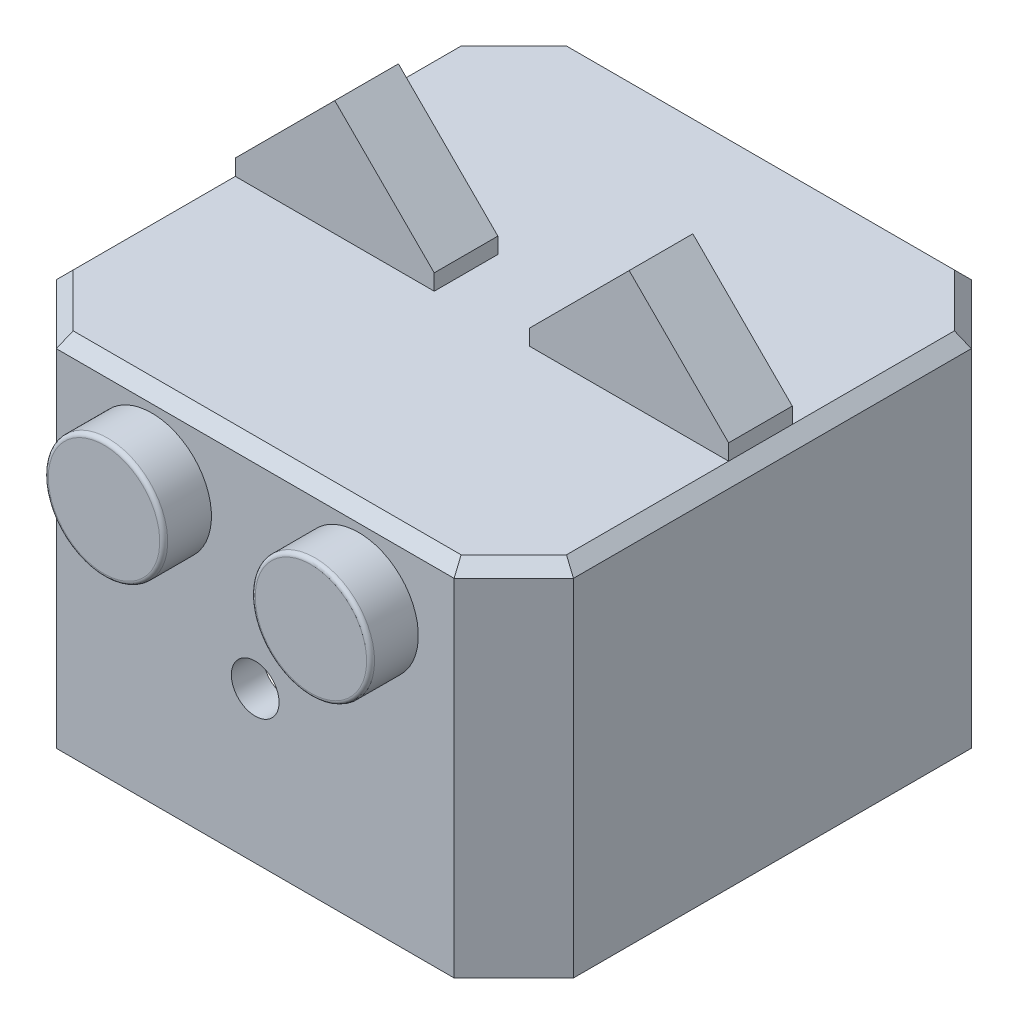
SolidWorks part; units mm, degrees
ref_plane "Alzado" through (0, 0, 0) normal (0, 0, 1) x (1, 0, 0)
ref_plane "Planta" through (0, 0, 0) normal (0, 1, 0) x (1, 0, 0)
ref_plane "Vista lateral" through (0, 0, 0) normal (1, 0, 0) x (0, 0, -1)
sketch "Croquis1" plane through (0, 0, 0) normal (0, 1, 0) x (1, 0, 0)
  line L1 (-25, -32.5) -> (25, -32.5)
  line L3 (-25, 32.5) -> (25, 32.5)
  line L5 (-25, -32.5) -> (25, 32.5) construction
  line L6 (-25, 32.5) -> (25, -32.5) construction
  line L10 (32.5, 25) -> (32.5, -25)
  line L11 (25, -32.5) -> (32.5, -25)
  line L12 (32.5, 25) -> (25, 32.5)
  line L13 (-32.5, 25) -> (-32.5, -25)
  line L14 (-32.5, -25) -> (-25, -32.5)
  line L15 (-32.5, 25) -> (-25, 32.5)
  point P0 (0, 0)
  point P10 (0, 32.5)
  dimension "D1" = 65
  dimension "D2" = 65
  dimension "D3" = 50
  dimension "D4" = 50
  dimension "D5" = 25
  dimension "D6" = 25
extrude "Saliente-Extruir1" add sketch "Croquis1" along normal blind 45
shell "Vaciado2" thickness 4 removed face at (0, 0, 0)
chamfer "Chaflán3" distance 1.5 angle 45 8 edges at (0, 45, -32.5) (32.5, 45, 0) (0, 45, 32.5) (-32.5, 45, 0) (-28.75, 45, 28.75) (28.75, 45, 28.75) (28.75, 45, -28.75) (-28.75, 45, -28.75)
sketch "Croquis2" plane through (0, 0, 32.5) normal (0, 0, 1) x (1, 0, 0)
  line L0 (0, 0) -> (0, 6.916) construction
  circle A0 centre (13, 35) radius 7.5
  circle A1 centre (-13, 35) radius 7.5
  dimension "D1" = 15
  dimension "D2" = 13
  dimension "D3" = 35
extrude "Saliente-Extruir2" add sketch "Croquis2" along normal blind 6
sketch "Croquis4" plane through (0, 0, 28.5) normal (0, 0, -1) x (-1, 0, 0)
  line L0 (0, 0) -> (0, 4.7403) construction
  line L1 (0, 0) -> (0, 6.916) construction
  circle A0 centre (-13, 35) radius 5
  circle A1 centre (13, 35) radius 5
  dimension "D1" = 10
extrude "Cortar-Extruir2" cut sketch "Croquis4" against normal blind 5.5
fillet "Redondeo1" radius 0.5 2 edges at (-20.5, 35, 38.5) (20.5, 35, 38.5)
sketch "Croquis5" plane through (0, 0, 32.5) normal (0, 0, 1) x (1, 0, 0)
  circle A0 centre (0, 19) radius 3
  dimension "D2" = 6
  dimension "D1" = 19
extrude "Cortar-Extruir3" cut sketch "Croquis5" against normal blind 10
sketch "Croquis13" plane through (0, 0, 34) normal (0, 0, -1) x (-1, 0, 0)
  circle A0 centre (-13, 35) radius 2.6
  circle A1 centre (13, 35) radius 2.6
  circle A2 centre (13, 35) radius 5
  circle A3 centre (-13, 35) radius 5
  dimension "D1" = 5.2
  dimension "D2" = 5.2
extrude "Saliente-Extruir8" add sketch "Croquis13" along normal blind 5.5
sketch "Croquis7" plane through (0, 0, 28.5) normal (0, 0, -1) x (-1, 0, 0)
  line L0 (23.3431, 0) -> (-23.3431, 0) construction
  line L1 (-13.58, 8.5) -> (-9.58, 8.5)
  line L2 (-13.58, 8.5) -> (-13.58, 12.5)
  line L3 (-13.58, 12.5) -> (-9.58, 12.5)
  line L4 (-9.58, 8.5) -> (-9.58, 12.5)
  line L5 (-13.58, 8.5) -> (-9.58, 12.5) construction
  line L6 (-13.58, 12.5) -> (-9.58, 8.5) construction
  line L8 (-13.58, 26) -> (-9.58, 26)
  line L9 (-13.58, 26) -> (-13.58, 30)
  line L10 (-13.58, 30) -> (-9.58, 30)
  line L11 (-9.58, 26) -> (-9.58, 30)
  line L12 (-13.58, 26) -> (-9.58, 30) construction
  line L13 (-13.58, 30) -> (-9.58, 26) construction
  line L14 (13.43, 12.5) -> (9.43, 8.5) construction
  line L15 (13.43, 8.5) -> (9.43, 12.5) construction
  line L16 (9.43, 8.5) -> (9.43, 12.5)
  line L17 (13.43, 12.5) -> (9.43, 12.5)
  line L18 (13.43, 8.5) -> (13.43, 12.5)
  line L19 (13.43, 8.5) -> (9.43, 8.5)
  line L20 (13.43, 30) -> (9.43, 26) construction
  line L21 (13.43, 26) -> (9.43, 30) construction
  line L22 (9.43, 26) -> (9.43, 30)
  line L23 (13.43, 30) -> (9.43, 30)
  line L24 (13.43, 26) -> (13.43, 30)
  line L25 (13.43, 26) -> (9.43, 26)
  point P0 (-11.58, 10.5)
  point P8 (-11.58, 28)
  point P13 (0, 0)
  point P15 (11.43, 10.5)
  point P16 (11.43, 28)
  point P20 (11.43, 10.5)
  point P25 (11.43, 28)
  point P26 (-11.58, 28)
  point P27 (11.43, 28)
  point P28 (11.43, 10.5)
  point P29 (-11.58, 10.5)
  dimension "D1" = 10.5
  dimension "D2" = 4
  dimension "D3" = 4
  dimension "D4" = 11.58
  dimension "D5" = 4
  dimension "D6" = 4
  dimension "D7" = 28
  dimension "D8" = 23.01
  dimension "D9" = 23.01
  dimension "D10" = 4
  dimension "D11" = 4
  dimension "D12" = 4
  dimension "D13" = 4
  dimension "D14" = 10.5
  dimension "D15" = 28
extrude "Saliente-Extruir3" add sketch "Croquis7" along normal blind 1
sketch "Croquis8" plane through (0, 0, 27.5) normal (0, 0, -1) x (-1, 0, 0)
  line L0 (0, 0) -> (0, 4.8013) construction
  line L1 (23.3431, 0) -> (-23.3431, 0) construction
  circle A0 centre (-11.505, 10.4893) radius 2
  circle A1 centre (-11.505, 27.9763) radius 2
  circle A2 centre (11.505, 10.4893) radius 2
  circle A3 centre (11.505, 27.9763) radius 2
  dimension "D1" = 4
  dimension "D2" = 4
  dimension "D3" = 23.01
  dimension "D4" = 23.01
extrude "Saliente-Extruir4" add sketch "Croquis8" along normal blind 1
sketch "Croquis9" plane through (0, 0, 26.5) normal (0, 0, -1) x (-1, 0, 0)
  circle A0 centre (-11.505, 27.9763) radius 1.6
  circle A1 centre (-11.505, 10.4893) radius 1.6
  circle A2 centre (11.505, 10.4893) radius 1.6
  circle A3 centre (11.505, 27.9763) radius 1.6
  dimension "D1" = 3.2
  dimension "D2" = 3.2
  dimension "D3" = 3.2
  dimension "D4" = 3.2
extrude "Cortar-Extruir5" cut sketch "Croquis9" against normal blind 2
sketch "Croquis10" plane through (0, 45, 0) normal (0, 1, 0) x (1, 0, 0)
  line L0 (-31, 24.3787) -> (-31, -24.3787) construction
  line L1 (-31, -4) -> (-6, -4)
  line L2 (-31, -4) -> (-31, 4)
  line L3 (-31, 4) -> (-6, 4)
  line L4 (-6, -4) -> (-6, 4)
  line L5 (-31, -4) -> (-6, 4) construction
  line L6 (-31, 4) -> (-6, -4) construction
  line L7 (0, 0) -> (0, 7.307) construction
  line L8 (31, 4) -> (6, -4) construction
  line L9 (31, -4) -> (6, 4) construction
  line L10 (6, -4) -> (6, 4)
  line L11 (31, 4) -> (6, 4)
  line L12 (31, -4) -> (31, 4)
  line L13 (31, -4) -> (6, -4)
  point P0 (-18.5, 0)
  point P14 (18.5, 0)
  dimension "D1" = 25
  dimension "D2" = 8
extrude "Saliente-Extruir5" add sketch "Croquis10" along normal blind 2
sketch "Croquis11" plane through (0, 0, 4) normal (0, 0, 1) x (1, 0, 0)
  line L0 (-31, 47) -> (-6, 47)
  line L1 (-6, 47) -> (-18.5, 59.5)
  line L2 (-31, 47) -> (-18.5, 59.5)
  line L3 (0, 45) -> (0, 52) construction
  line L4 (-24.3787, 45) -> (24.3787, 45) construction
  line L5 (31, 47) -> (18.5, 59.5)
  line L6 (6, 47) -> (18.5, 59.5)
  line L7 (31, 47) -> (6, 47)
extrude "Saliente-Extruir6" add sketch "Croquis11" against normal blind 8
sketch "Croquis12" plane through (0, 41, 0) normal (0, -1, 0) x (1, 0, 0)
  line L0 (0, 0) -> (-5.199, 0) construction
  line L1 (-21.9, -8.93) -> (21.9, -8.93) construction
  line L2 (-21.9, -8.93) -> (-21.9, 8.93) construction
  line L3 (-21.9, 8.93) -> (21.9, 8.93) construction
  line L4 (21.9, -8.93) -> (21.9, 8.93) construction
  line L5 (-21.9, -8.93) -> (21.9, 8.93) construction
  line L6 (-21.9, 8.93) -> (21.9, -8.93) construction
  line L7 (0, 0) -> (0, 4.1573) construction
  circle A0 centre (-20.65, 7.68) radius 0.8
  circle A1 centre (-20.65, 7.68) radius 1.15
  circle A2 centre (-20.65, -7.68) radius 1.15
  circle A3 centre (-20.65, -7.68) radius 0.8
  circle A4 centre (20.65, 7.68) radius 1.15
  circle A5 centre (20.65, 7.68) radius 0.8
  circle A6 centre (20.65, -7.68) radius 1.15
  circle A7 centre (20.65, -7.68) radius 0.8
  point P0 (0, 0)
  dimension "D6" = 1.6
  dimension "D4" = 2.3
  dimension "D1" = 43.8
  dimension "D2" = 17.86
  dimension "D3" = 1.25
  dimension "D7" = 1.25
extrude "Saliente-Extruir7" add sketch "Croquis12" along normal blind 6
sketch "Croquis14" plane through (0, 41, 0) normal (0, -1, 0) x (1, 0, 0)
  line L1 (-22.15, 6.43) -> (-19.15, 6.43)
  line L2 (-22.15, 6.43) -> (-22.15, 8.93)
  line L3 (-22.15, 8.93) -> (-19.15, 8.93)
  line L4 (-19.15, 6.43) -> (-19.15, 8.93)
  line L5 (-22.15, 6.43) -> (-19.15, 8.93) construction
  line L6 (-22.15, 8.93) -> (-19.15, 6.43) construction
  line L7 (-22.15, -8.93) -> (-19.15, -8.93)
  line L8 (-22.15, -8.93) -> (-22.15, -6.43)
  line L9 (-22.15, -6.43) -> (-19.15, -6.43)
  line L10 (-19.15, -8.93) -> (-19.15, -6.43)
  line L11 (-22.15, -8.93) -> (-19.15, -6.43) construction
  line L12 (-22.15, -6.43) -> (-19.15, -8.93) construction
  line L13 (19.15, 6.43) -> (22.15, 6.43)
  line L14 (19.15, 6.43) -> (19.15, 8.93)
  line L15 (19.15, 8.93) -> (22.15, 8.93)
  line L16 (22.15, 6.43) -> (22.15, 8.93)
  line L17 (19.15, 6.43) -> (22.15, 8.93) construction
  line L18 (19.15, 8.93) -> (22.15, 6.43) construction
  line L19 (19.15, -8.93) -> (22.15, -8.93)
  line L20 (19.15, -8.93) -> (19.15, -6.43)
  line L21 (19.15, -6.43) -> (22.15, -6.43)
  line L22 (22.15, -8.93) -> (22.15, -6.43)
  line L23 (19.15, -8.93) -> (22.15, -6.43) construction
  line L24 (19.15, -6.43) -> (22.15, -8.93) construction
  point P0 (-20.65, 7.68)
  point P6 (-20.65, -7.68)
  point P12 (20.65, 7.68)
  point P18 (20.65, -7.68)
  dimension "D1" = 3
  dimension "D2" = 2.5
  dimension "D3" = 3
  dimension "D4" = 2.5
  dimension "D5" = 3
  dimension "D6" = 2.5
  dimension "D7" = 3
  dimension "D8" = 2.5
extrude "Saliente-Extruir9" add sketch "Croquis14" along normal blind 5
sketch "Croquis15" plane through (-32.5, 0, 0) normal (-1, 0, 0) x (0, 0, 1)
  line L1 (-6, 40.5) -> (6, 40.5)
  line L2 (-6, 40.5) -> (-6, 32.5)
  line L3 (-6, 32.5) -> (6, 32.5)
  line L4 (6, 40.5) -> (6, 32.5)
  dimension "D1" = 8
  dimension "D2" = 12
  dimension "D3" = 3
  dimension "D4" = 19
extrude "Cortar-Extruir6" cut sketch "Croquis15" against normal blind 2
sketch "Croquis16" plane through (0, 0, -28.5) normal (0, 0, 1) x (1, 0, 0)
  line L2 (18.95, 6.05) -> (6.55, 6.05)
  line L3 (18.95, 6.05) -> (18.95, 18.45)
  line L4 (18.95, 18.45) -> (6.55, 18.45)
  line L5 (6.55, 6.05) -> (6.55, 18.45)
  line L6 (5.5, 5) -> (20, 5)
  line L7 (5.5, 5) -> (5.5, 19.5)
  line L8 (5.5, 19.5) -> (20, 19.5)
  line L9 (20, 5) -> (20, 19.5)
  line L10 (5.5, 5) -> (20, 19.5) construction
  line L11 (5.5, 19.5) -> (20, 5) construction
  line L12 (18.95, 6.05) -> (6.55, 18.45) construction
  line L13 (18.95, 18.45) -> (6.55, 6.05) construction
  point P0 (12.75, 12.25)
  point P4 (12.75, 12.25)
  dimension "D1" = 12.4
  dimension "D2" = 12.4
  dimension "D3" = 5
  dimension "D4" = 5
  dimension "D5" = 14.5
  dimension "D6" = 14.5
extrude "Saliente-Extruir10" add sketch "Croquis16" along normal blind 3
sketch "Croquis17" plane through (0, 0, -28.5) normal (0, 0, 1) x (1, 0, 0)
  circle A0 centre (12.75, 12.25) radius 5.5
  point P2 (0, 0)
  point P4 (12.75, 12.25)
  dimension "D1" = 11
extrude "Cortar-Extruir7" cut sketch "Croquis17" against normal through all
